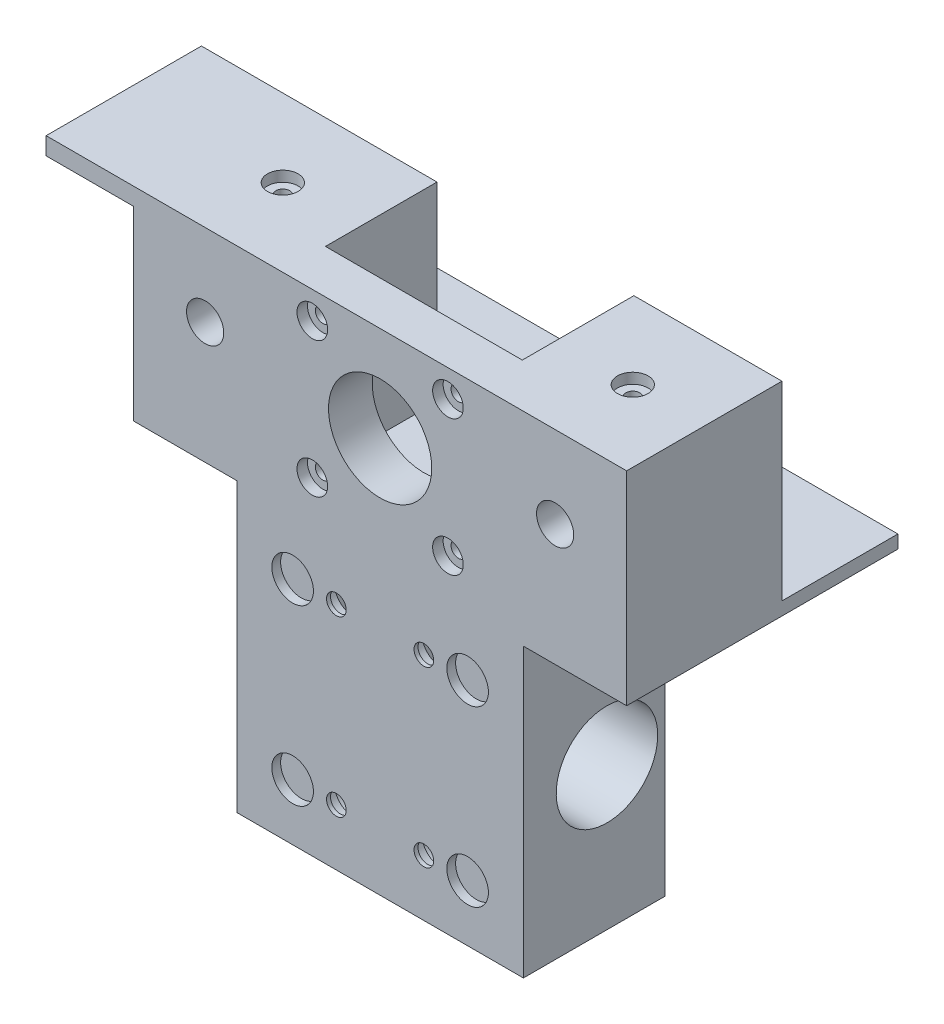
SolidWorks part; units mm, degrees
ref_plane "Front Plane" through (0, 0, 0) normal (0, 0, 1) x (1, 0, 0)
ref_plane "Top Plane" through (0, 0, 0) normal (0, 1, 0) x (1, 0, 0)
ref_plane "Right Plane" through (0, 0, 0) normal (1, 0, 0) x (0, 0, -1)
sketch "Sketch8" plane through (0, 0, 0) normal (0, 0, 1) x (1, 0, 0)
  line L0 (-22.5, -21.75) -> (22.5, -21.75) construction
  line L1 (-56.35, 0) -> (56.35, 0)
  line L2 (-56.35, 0) -> (-56.35, -46.5)
  line L3 (-56.35, -46.5) -> (56.35, -46.5)
  line L4 (56.35, 0) -> (56.35, -46.5)
  line L5 (22.5, -43.5) -> (56.35, -43.5)
  line L6 (-22.5, 0) -> (22.5, 0)
  line L7 (-76.35, 0) -> (-56.35, 0)
  line L9 (-56.35, 0) -> (-56.35, -4)
  line L10 (-56.35, -4) -> (-76.35, -4)
  line L11 (-76.35, 0) -> (-76.35, -4)
  line L12 (0, 0) -> (0, -46.5) construction
  line L13 (-32.75, -46.5) -> (32.75, -46.5)
  line L14 (-32.75, -46.5) -> (-32.75, -112.2)
  line L15 (-32.75, -112.2) -> (32.75, -112.2)
  line L16 (32.75, -46.5) -> (32.75, -112.2)
  line L17 (-22.5, 0) -> (-22.5, -43.5)
  line L18 (-22.5, -43.5) -> (22.5, -43.5)
  line L19 (22.5, 0) -> (22.5, -43.5)
  line L20 (-22.5, 0) -> (22.5, -43.5) construction
  line L21 (-22.5, -43.5) -> (22.5, 0) construction
  line L22 (-22.5, -43.5) -> (-56.35, -43.5)
  circle A0 centre (-40, -18.75) radius 4.25
  circle A1 centre (0, -21.75) radius 11.8
  circle A2 centre (40, -18.75) radius 4.25
  point P4 (0, 0)
  point P15 (-15.5, -6.25)
  point P16 (0, -112.2)
  point P20 (0, -21.75)
  point P28 (-15.5, -37.25)
  point P29 (15.5, -37.25)
  point P30 (15.5, -6.25)
  dimension "D13" = 8.5
  dimension "D14" = 23.6
  dimension "D1" = 112.7
  dimension "D2" = 46.5
  dimension "D3" = 20
  dimension "D4" = 4
  dimension "D5" = 65.5
  dimension "D6" = 65.7
  dimension "D7" = 40
  dimension "D8" = 3
  dimension "D9" = 45
  dimension "D10" = 15.5
  dimension "D11" = 15.5
  dimension "D12" = 3
extrude "Boss-Extrude6" add sketch "Sketch8" against normal blind 4 separate body contours L16 L3 L14 L15 region at (0, -79.35, 0)
extrude "Boss-Extrude7" add sketch "Sketch8<3>" against normal blind 35.5 separate body contours L22 L17 L1 L2 A0 | L1 L19 L5 L4 A2 region at (-39.425, -0.5512, 0) region at (39.425, -0.5512, 0)
sketch "Sketch8<3>" plane through (0, 0, 0) normal (0, 0, 1) x (1, 0, 0) same geometry as "Sketch8"
extrude "Boss-Extrude8" add sketch "Sketch8<4>" against normal blind 10 contours L19 L1 L17 L18 A1 region at (0, -0.6259, 0)
sketch "Sketch8<4>" plane through (0, 0, 0) normal (0, 0, 1) x (1, 0, 0) same geometry as "Sketch8"
extrude "Boss-Extrude9" add sketch "Sketch8<5>" against normal blind 62 contours L18 L22 L2 L3 L4 L5 region at (0, -45, 0)
sketch "Sketch8<5>" plane through (0, 0, 0) normal (0, 0, 1) x (1, 0, 0) same geometry as "Sketch8"
extrude "Boss-Extrude10" add sketch "Sketch8<6>" against normal up to surface (35.5 mm away) contours L7 L11 L10 L2 region at (-66.35, -2, 0) up to face at (-35.75, -18.75, -35.5)
sketch "Sketch8<6>" plane through (0, 0, 0) normal (0, 0, 1) x (1, 0, 0) same geometry as "Sketch8"
sketch "Sketch11" plane through (0, 0, 0) normal (0, 0, 1) x (1, 0, 0)
  line L0 (11.8, -21.75) -> (-11.8, -21.75) construction
  line L1 (0, -33.55) -> (0, -9.95) construction
  circle A0 centre (0, -21.75) radius 11.8 construction
  point P0 (0, -21.75)
  point P1 (-15.5, -6.25)
  point P9 (15.5, -6.25)
  point P11 (15.5, -37.25)
  point P12 (-15.5, -37.25)
  dimension "D1" = 15.5
  dimension "D2" = 15.5
hole_wizard "CBORE for M3 Pan Head Machine Screw2" positions "3DSketch3" profile "Sketch12" counterbore size "M3" standard "ANSI Metric" end condition up to next
sketch3d "3DSketch3"
  point P0 (-15.5, -6.25, 0)
  point P3 (15.5, -6.25, 0)
  point P6 (15.5, -37.25, 0)
  point P9 (-15.5, -37.25, 0)
sketch "Sketch12" plane through (-15.5, -6.25, 0) normal (1, 0, 0) x (0, -1, 0)
  line L0 (0, 0) -> (0, 10)
  line L1 (0, 10) -> (1.7, 10)
  line L3 (1.7, 10) -> (1.7, 2.4)
  line L4 (1.7, 2.4) -> (3.5, 2.4)
  line L5 (3.5, 2.4) -> (3.5, 0)
  line L7 (3.5, 0) -> (0, 0)
  line L11 (0, -6.35) -> (0, 107.95) construction
  dimension "Thru Hole Dia." = 3.4
  dimension "Thru Hole Depth" = 10
  dimension "C'Bore Dia." = 7
  dimension "C'Bore Depth" = 2.4
sketch "Sketch13" plane through (0, 0, 0) normal (0, 0, 1) x (1, 0, 0)
  line L0 (-32.75, -46.5) -> (-32.75, -112.2) construction
  line L1 (32.75, -112.2) -> (-32.75, -112.2)
  line L2 (32.75, -112.2) -> (32.75, -46.7)
  line L3 (32.75, -46.7) -> (-32.75, -46.7)
  line L4 (-32.75, -112.2) -> (-32.75, -46.7)
  line L5 (-32.75, -79.45) -> (32.75, -79.45) construction
  line L6 (0, -112.2) -> (0, -46.7) construction
  circle A0 centre (-20, -99.3) radius 4.75
  circle A1 centre (-20, -59.6) radius 4.75
  circle A2 centre (20, -59.6) radius 4.75
  circle A3 centre (20, -99.3) radius 4.75
  point P7 (-20, -99.3)
  point P8 (20, -99.3)
  point P9 (20, -59.6)
  point P12 (-20, -59.6)
  dimension "D6" = 9.5
  dimension "D1" = 65.5
  dimension "D2" = 12.9
  dimension "D3" = 12.75
  dimension "D4" = 12.75
  dimension "D5" = 52.6
extrude "Cut-Extrude1" cut sketch "Sketch13" against normal blind 2 contours A1 | A3 | A0 | A2 region at (-20, -99.3, 0) region at (-20, -59.6, 0) region at (20, -99.3, 0)
sketch "Sketch14" plane through (0, 0, -4) normal (0, 0, -1) x (-1, 0, 0)
  line L0 (32.75, -112.2) -> (-32.75, -112.2) construction
  line L1 (15.25, -97.25) -> (-15.25, -97.25)
  line L2 (15.25, -97.25) -> (15.25, -61.65)
  line L3 (15.25, -61.65) -> (-15.25, -61.65)
  line L4 (-15.25, -97.25) -> (-15.25, -61.65)
  line L5 (-32.75, -46.5) -> (-32.75, -112.2) construction
  line L6 (32.75, -112.2) -> (-32.75, -112.2) construction
  line L7 (32.75, -112.2) -> (32.75, -46.7) construction
  line L8 (32.75, -46.7) -> (-32.75, -46.7) construction
  line L9 (-32.75, -112.2) -> (-32.75, -46.7) construction
  line L11 (-15.25, -79.45) -> (15.25, -79.45) construction
  line L12 (0, -61.65) -> (0, -97.25) construction
  circle A0 centre (-10, -59.6) radius 5
  circle A1 centre (10, -59.6) radius 5
  circle A2 centre (10, -99.3) radius 5
  circle A3 centre (-10, -99.3) radius 5
  point P4 (0, -61.65)
  point P7 (0, -112.2)
  point P15 (-15.25, -79.45)
  point P16 (-32.75, -79.45)
  point P17 (10, -59.6)
  point P22 (-10, -59.6)
  point P24 (10, -99.3)
  point P25 (-10, -99.3)
  line M6 (-32.75, -46.5) -> (-32.75, -112.2)
  line M7 (-32.75, -112.2) -> (32.75, -112.2)
  line M8 (32.75, -112.2) -> (32.75, -46.5)
  line M9 (32.75, -46.5) -> (-32.75, -46.5)
  dimension "D6" = 10
  dimension "D1" = 35.6
  dimension "D2" = 30.5
  dimension "D3" = 65.5
  dimension "D4" = 10
  dimension "D5" = 19.85
hole_wizard "CBORE for M4 Pan Head Machine Screw1" positions "3DSketch4" profile "Sketch15" counterbore size "M4" standard "ANSI Metric" end condition up to next
sketch3d "3DSketch4"
  point P0 (10, -59.6, -4)
  point P3 (-10, -59.6, -4)
  point P6 (10, -99.3, -4)
  point P9 (-10, -99.3, -4)
sketch "Sketch15" plane through (10, -59.6, -4) normal (1, 0, 0) x (0, 1, 0)
  line L0 (0, 0) -> (0, 4)
  line L1 (0, 4) -> (2.25, 4)
  line L3 (2.25, 4) -> (2.25, 3.1)
  line L4 (2.25, 3.1) -> (4.5, 3.1)
  line L5 (4.5, 3.1) -> (4.5, 0)
  line L7 (4.5, 0) -> (0, 0)
  line L11 (0, -6.35) -> (0, 107.95) construction
  dimension "Thru Hole Dia." = 4.5
  dimension "Thru Hole Depth" = 4
  dimension "C'Bore Dia." = 9
  dimension "C'Bore Depth" = 3.1
extrude "Boss-Extrude11" add sketch "Sketch14" along normal blind 28.4 contours L1 A3 L4 L3 A0 A1 L2 A2 M9 M6 M7 M8 region at (0, -47.4277, -4)
sketch "Sketch17" plane through (32.75, 0, 0) normal (1, 0, 0) x (0, 0, -1)
  line L0 (0, -46.5) -> (0, -112.2) construction
  line L1 (32.4, -112.2) -> (0, -112.2) construction
  circle A0 centre (19.1, -79.45) radius 11.6
  dimension "D3" = 23.2
  dimension "D1" = 19.1
  dimension "D2" = 32.75
extrude "Cut-Extrude2" cut sketch "Sketch17" against normal up to next
sketch "Sketch19" plane through (-32.75, 0, 0) normal (-1, 0, 0) x (0, 0, 1)
  line L0 (-32.4, -112.2) -> (0, -112.2) construction
  line L1 (0, -46.5) -> (0, -112.2) construction
  circle A0 centre (-19.1, -79.45) radius 5.25
  dimension "D3" = 10.5
  dimension "D1" = 32.75
  dimension "D2" = 19.1
extrude "Cut-Extrude3" cut sketch "Sketch19" against normal up to next
sketch "Sketch20" plane through (0, 0, 0) normal (0, 0, 1) x (1, 0, 0)
  line L0 (40, -18.75) -> (40, 0) construction
  line L1 (-76.35, 0) -> (56.35, 0) construction
  line L2 (-40, -18.75) -> (-40, 0) construction
sketch "Sketch21" plane through (0, 0, 0) normal (0, 1, 0) x (1, 0, 0)
  line L0 (40, 0) -> (40, 35.5) construction
  line L1 (22.5, 35.5) -> (56.35, 35.5) construction
  line L2 (-40, 0) -> (-40, 35.5) construction
  line L3 (-76.35, 35.5) -> (-22.5, 35.5) construction
  point P10 (40, 17.75)
  point P11 (-40, 17.75)
hole_wizard "CBORE for M3 Pan Head Machine Screw3" positions "3DSketch6" profile "Sketch23" counterbore size "M3" standard "ANSI Metric" end condition up to next
sketch3d "3DSketch6"
  point P0 (40, 0, -17.75)
  point P3 (-40, 0, -17.75)
sketch "Sketch23" plane through (40, 0, -17.75) normal (1, 0, 0) x (0, 0, 1)
  line L0 (0, 0) -> (0, 14.5)
  line L1 (0, 14.5) -> (1.6, 14.5)
  line L3 (1.6, 14.5) -> (1.6, 2.4)
  line L4 (1.6, 2.4) -> (3.5, 2.4)
  line L5 (3.5, 2.4) -> (3.5, 0)
  line L7 (3.5, 0) -> (0, 0)
  line L11 (0, -6.35) -> (0, 107.95) construction
  dimension "Thru Hole Dia." = 3.2
  dimension "Thru Hole Depth" = 14.5
  dimension "C'Bore Dia." = 7
  dimension "C'Bore Depth" = 2.4
